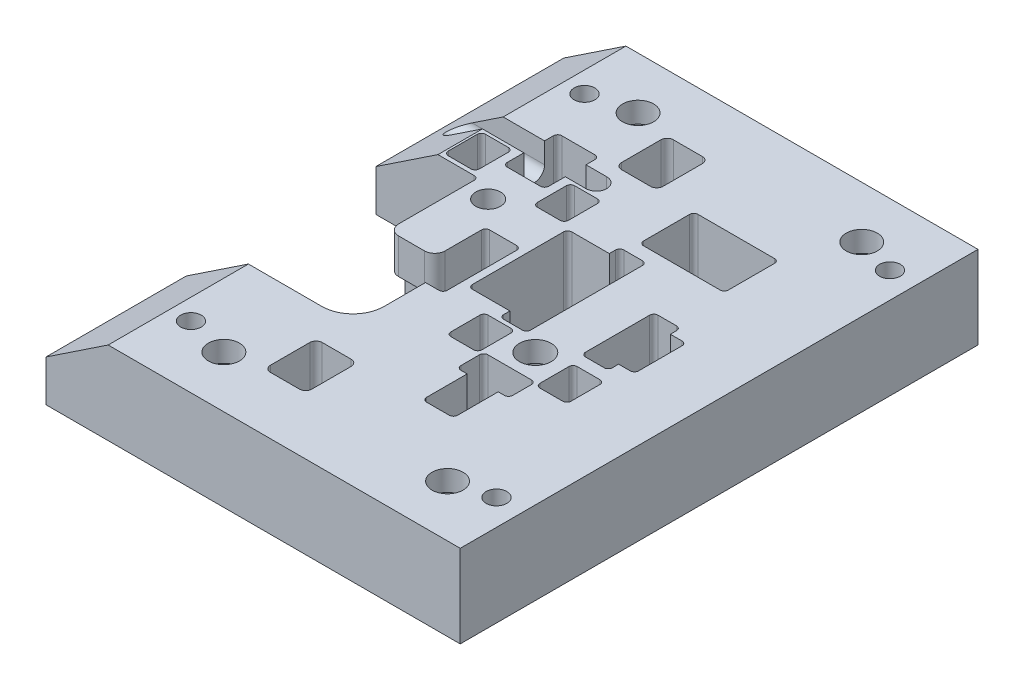
SolidWorks part; units mm, degrees
material "K110"
ref_plane "Front Plane" through (0, 0, 0) normal (0, 0, 1) x (1, 0, 0)
ref_plane "Top Plane" through (0, 0, 0) normal (0, 1, 0) x (1, 0, 0)
ref_plane "Right Plane" through (0, 0, 0) normal (1, 0, 0) x (0, 0, -1)
sketch "Sketch1" plane through (0, 0, 0) normal (0, 1, 0) x (1, 0, 0)
  line L1 (-100, -125) -> (100, -125)
  line L2 (-100, -125) -> (-100, 125)
  line L3 (-100, 125) -> (100, 125)
  line L4 (100, -125) -> (100, 125)
  line L5 (-100, -125) -> (100, 125) construction
  line L6 (-100, 125) -> (100, -125) construction
  point P0 (0, 0)
  dimension "D1" = 250
  dimension "D2" = 200
extrude "Boss-Extrude1" add sketch "Sketch1" along normal blind 40
sketch "Sketch2" plane through (0, 40, 0) normal (0, 1, 0) x (1, 0, 0)
  line L0 (17.25, 55.73) -> (55.25, 55.73) construction
  line L1 (15.75, 32.73) -> (15.75, -12.27) construction
  line L2 (58.25, 13.73) -> (58.25, -8.27) construction
  line L3 (30.25, -47.4) -> (42.25, -47.4) construction
  line L4 (17.25, 55.73) -> (55.25, 55.73)
  line L5 (15.75, 32.73) -> (15.75, -12.27)
  line L6 (58.25, 13.73) -> (58.25, -8.27)
  line L7 (30.25, -47.4) -> (42.25, -47.4)
sketch "Sketch3" plane through (0, 40, 0) normal (0, 1, 0) x (1, 0, 0)
  line L0 (30.25, -47.4) -> (42.25, -47.4) construction
  line L1 (28.75, -72.03) -> (43.75, -72.03)
  line L2 (28.75, -72.03) -> (28.75, -50.4)
  line L3 (23.75, -37.4) -> (48.75, -37.4)
  line L4 (43.75, -72.03) -> (43.75, -50.4)
  line L8 (36.25, -37.4) -> (36.25, -72.03) construction
  line L9 (36.25, 69.53) -> (36.25, -69.53) construction
  line L11 (43.75, -50.4) -> (48.75, -50.4)
  line L12 (48.75, -50.4) -> (48.75, -37.4)
  line L13 (28.75, -50.4) -> (23.75, -50.4)
  line L14 (23.75, -50.4) -> (23.75, -37.4)
  line L15 (66.38, -69.53) -> (-4.87, -69.53) construction
  dimension "D1" = 10
  dimension "D2" = 15
  dimension "D3" = 3
  dimension "D4" = 25
  dimension "D5" = 2.5
extrude "Cut-Extrude2" cut sketch "Sketch3" against normal up to next contours L3 L12 L11 L4 L1 L2 L13 L14
fillet "Fillet3" radius 2 6 edges at (43.75, 20, 72.03) (28.75, 20, 72.03) (48.75, 20, 50.4) (23.75, 20, 50.4) (48.75, 20, 37.4) (23.75, 20, 37.4)
sketch "Sketch4" plane through (0, 40, 0) normal (0, 1, 0) x (1, 0, 0)
  line L0 (48.25, -14.77) -> (61.25, -14.77)
  line L5 (61.25, -14.77) -> (61.25, -9.77)
  line L6 (64.38, 13.73) -> (58.25, 13.73) construction
  line L7 (66.38, 69.53) -> (66.38, -69.53) construction
  line L8 (66.38, 2.73) -> (51.7072, 2.73) construction
  line L9 (66.38, -6.27) -> (66.38, 11.73) construction
  line L10 (61.25, -9.77) -> (68.88, -9.77)
  line L11 (68.88, -9.77) -> (68.88, 15.23)
  line L13 (68.88, 15.23) -> (61.25, 15.23)
  line L14 (61.25, 15.23) -> (61.25, 20.23)
  line L15 (61.25, 20.23) -> (48.25, 20.23)
  line L16 (48.25, 20.23) -> (48.25, -14.77)
  line L17 (58.25, 13.73) -> (58.25, -8.27) construction
  dimension "D1" = 1.5
  dimension "D2" = 5
  dimension "D3" = 2.5
  dimension "D4" = 10
  dimension "D5" = 3
extrude "Cut-Extrude3" cut sketch "Sketch4" against normal up to next
fillet "Fillet4" radius 2 6 edges at (68.88, 20, 9.77) (68.88, 20, -15.23) (61.25, 20, -20.23) (48.25, 20, -20.23) (48.25, 20, 14.77) (61.25, 20, 14.77)
sketch "Sketch5" plane through (0, 40, 0) normal (0, 1, 0) x (1, 0, 0)
  line L0 (-7.37, -13.77) -> (12.75, -13.77)
  line L2 (12.75, -18.77) -> (25.75, -18.77)
  line L3 (25.75, -18.77) -> (25.75, 39.23)
  line L4 (25.75, 39.23) -> (12.75, 39.23)
  line L5 (12.75, 39.23) -> (12.75, 34.23)
  line L6 (12.75, 34.23) -> (-7.37, 34.23)
  line L7 (-7.37, 34.23) -> (-7.37, -13.77)
  line L8 (15.75, 32.73) -> (15.75, -12.27) construction
  line L9 (-4.87, 69.53) -> (-4.87, -69.53) construction
  line L10 (-4.87, 10.23) -> (25.75, 10.23) construction
  line L11 (-4.87, 26.73) -> (-4.87, -6.27) construction
  line L12 (12.75, -18.77) -> (12.75, -13.77)
  line L13 (1.13, -12.27) -> (15.75, -12.27) construction
  line L17 (-18, -8.27) -> (-18, 13.73) construction
  line L18 (-18, 2.73) -> (-15, 2.73) construction
  dimension "D1" = 3
  dimension "D2" = 10
  dimension "D3" = 2.5
  dimension "D4" = 1.5
  dimension "D5" = 5
extrude "Cut-Extrude4" cut sketch "Sketch5" against normal up to next
fillet "Fillet5" radius 2 6 edges at (25.75, 20, -39.23) (12.75, 20, 18.77) (25.75, 20, 18.77) (-7.37, 20, 13.77) (12.75, 20, -39.23) (-7.37, 20, -34.23)
sketch "Sketch6" plane through (0, 40, 0) normal (0, 1, 0) x (1, 0, 0)
  line L0 (15.75, 72.03) -> (15.75, 45.73)
  line L3 (15.75, 45.73) -> (56.75, 45.73)
  line L6 (56.75, 45.73) -> (56.75, 72.03)
  line L7 (56.75, 72.03) -> (15.75, 72.03)
  line L8 (36.25, 69.53) -> (36.25, 45.73) construction
  line L9 (36.25, 69.53) -> (36.25, -69.53) construction
  line L10 (66.38, 69.53) -> (-4.87, 69.53) construction
  line L12 (17.25, 55.73) -> (55.25, 55.73) construction
  dimension "D1" = 2.5
  dimension "D2" = 41
  dimension "D5" = 10
extrude "Cut-Extrude5" cut sketch "Sketch6" against normal up to next
fillet "Fillet6" radius 2 4 edges at (15.75, 20, -72.03) (56.75, 20, -72.03) (15.75, 20, -45.73) (56.75, 20, -45.73)
sketch "Sketch7" plane through (0, 40, 0) normal (0, 1, 0) x (1, 0, 0)
  line L0 (57.75, -29.77) -> (57.75, -32.27) construction
  line L3 (60.25, -29.77) -> (55.25, -29.77) construction
  line L4 (60.25, -27.27) -> (60.25, -32.27) construction
  line L5 (55.25, -11.27) -> (55.25, -38.4) construction
  line L7 (63.25, -20.77) -> (52.25, -20.77)
  line L8 (65.25, -22.77) -> (65.25, -36.77)
  line L9 (63.25, -38.77) -> (52.25, -38.77)
  line L10 (50.25, -22.77) -> (50.25, -36.77)
  arc A2 (52.25, -38.77) -> (50.25, -36.77) centre (52.25, -36.77) cw
  arc A3 (65.25, -36.77) -> (63.25, -38.77) centre (63.25, -36.77) cw
  arc A4 (63.25, -20.77) -> (65.25, -22.77) centre (63.25, -22.77) cw
  arc A5 (52.25, -20.77) -> (50.25, -22.77) centre (52.25, -22.77) ccw
  point P14 (50.25, -38.77)
  point P17 (65.25, -38.77)
  point P20 (65.25, -20.77)
  dimension "D4" = 2
  dimension "D1" = 2.5
  dimension "D2" = 18
  dimension "D3" = 15
  dimension "D5" = 9
extrude "Cut-Extrude6" cut sketch "Sketch7" against normal up to next
sketch "Sketch8" plane through (0, 40, 0) normal (0, 1, 0) x (1, 0, 0)
  line L0 (12.25, -29.77) -> (17.25, -29.77) construction
  line L3 (12.25, -32.27) -> (12.25, -27.27) construction
  line L4 (63.25, -20.77) -> (52.25, -20.77) construction
  line L7 (17.25, -38.4) -> (17.25, -13.77) construction
  line L8 (14.75, -29.77) -> (14.75, -32.27) construction
  line L9 (52.25, -38.77) -> (63.25, -38.77) construction
  line L10 (9.25, -20.77) -> (20.25, -20.77)
  line L11 (7.25, -22.77) -> (7.25, -36.77)
  line L12 (9.25, -38.77) -> (20.25, -38.77)
  line L13 (22.25, -22.77) -> (22.25, -36.77)
  arc A2 (7.25, -36.77) -> (9.25, -38.77) centre (9.25, -36.77) ccw
  arc A3 (20.25, -38.77) -> (22.25, -36.77) centre (20.25, -36.77) ccw
  arc A4 (20.25, -20.77) -> (22.25, -22.77) centre (20.25, -22.77) cw
  arc A5 (9.25, -20.77) -> (7.25, -22.77) centre (9.25, -22.77) ccw
  dimension "D1" = 2.5
  dimension "D2" = 2
extrude "Cut-Extrude7" cut sketch "Sketch8" against normal up to next
sketch "Sketch21" plane through (0, 40, 0) normal (0, 1, 0) x (1, 0, 0)
  line L0 (-21, 55.73) -> (-21, 16.73) construction
  line L3 (-24, 54.23) -> (-13, 54.23)
  line L4 (-26, 52.23) -> (-26, 38.23)
  line L5 (-24, 36.23) -> (-13, 36.23)
  line L6 (-11, 52.23) -> (-11, 38.23)
  line L7 (-21, 55.73) -> (-59, 55.73) construction
  line L9 (-16, 45.23) -> (-21, 45.23) construction
  line L10 (-18.5, 45.23) -> (-18.5, 54.23) construction
  line L11 (-40, 55.73) -> (-40, 36.23) construction
  line L12 (-16, 42.73) -> (-16, 47.73) construction
  line L16 (-69, 52.23) -> (-69, 38.23)
  line L17 (-56, 36.23) -> (-67, 36.23)
  line L18 (-54, 52.23) -> (-54, 38.23)
  line L19 (-56, 54.23) -> (-67, 54.23)
  arc A2 (-26, 38.23) -> (-24, 36.23) centre (-24, 38.23) ccw
  arc A3 (-13, 36.23) -> (-11, 38.23) centre (-13, 38.23) ccw
  arc A4 (-13, 54.23) -> (-11, 52.23) centre (-13, 52.23) cw
  arc A5 (-24, 54.23) -> (-26, 52.23) centre (-24, 52.23) ccw
  arc A6 (-56, 54.23) -> (-54, 52.23) centre (-56, 52.23) cw
  arc A7 (-67, 54.23) -> (-69, 52.23) centre (-67, 52.23) ccw
  arc A8 (-67, 36.23) -> (-69, 38.23) centre (-67, 38.23) cw
  arc A9 (-54, 38.23) -> (-56, 36.23) centre (-56, 38.23) cw
  dimension "D4" = 15
  dimension "D2" = 2
  dimension "D1" = 2.5
  dimension "D3" = 18
extrude "Cut-Extrude12" cut sketch "Sketch21" against normal up to next
sketch "Sketch22" plane through (0, 40, 0) normal (0, 1, 0) x (1, 0, 0)
  line L0 (-100, 125) -> (-100, -125) construction
  line L1 (-100, 55.73) -> (-15, 55.73)
  line L2 (-100, 55.73) -> (-100, 65.726)
  line L3 (-100, 65.726) -> (-15, 65.726)
  line L4 (-15, 55.73) -> (-15, 65.726)
  line L5 (-21, 55.73) -> (-59, 55.73) construction
  line L6 (-59, 63.776) -> (-21, 63.776) construction
  line L7 (-21, 55.73) -> (-21, 61.5256) construction
  line L8 (-15, 60.728) -> (-100, 60.728) construction
  dimension "D1" = 1.95
  dimension "D2" = 6
ref_plane "Plane1" through (0, 0, -60.728) normal (0, 0, -1) x (-1, 0, 0)
sketch "Sketch24" plane through (0, 0, -60.728) normal (0, 0, -1) x (-1, 0, 0)
  line L0 (15, 40) -> (15, 35)
  line L1 (15, 40) -> (100, 40) construction
  line L2 (25, 25) -> (100, 25)
  line L3 (100, 40) -> (100, 0) construction
  line L4 (15, 40) -> (100, 40)
  line L5 (100, 40) -> (100, 25)
  arc A0 (15, 35) -> (25, 25) centre (25, 35) ccw
  dimension "D2" = 10
  dimension "D1" = 15
extrude "Cut-Extrude15" cut sketch "Sketch24" against normal mid plane 10
fillet "Fillet9" 2 edges at (-62.5, 25, -55.728) (-62.5, 25, -65.728) type full round first side face at (-50.5858, 32.5858, -55.728) second side face at (-50.5858, 32.5858, -65.728) middle face at (-62.5, 25, -60.728)
sketch "Sketch23" plane through (0, 40, 0) normal (0, 1, 0) x (1, 0, 0)
  line L0 (-40, 55.73) -> (-40, 45.73) construction
  line L1 (-48, 72.03) -> (-32, 72.03)
  line L2 (-50, 70.03) -> (-50, 47.73)
  line L3 (-48, 45.73) -> (-32, 45.73)
  line L4 (-30, 70.03) -> (-30, 47.73)
  line L5 (-21, 55.73) -> (-59, 55.73) construction
  line L6 (17.75, 45.73) -> (54.75, 45.73) construction
  line L7 (54.75, 72.03) -> (17.75, 72.03) construction
  arc A0 (-50, 47.73) -> (-48, 45.73) centre (-48, 47.73) ccw
  arc A1 (-48, 72.03) -> (-50, 70.03) centre (-48, 70.03) ccw
  arc A2 (-32, 72.03) -> (-30, 70.03) centre (-32, 70.03) cw
  arc A3 (-32, 45.73) -> (-30, 47.73) centre (-32, 47.73) ccw
  point P14 (-50, 45.73)
  point P21 (-30, 45.73)
  dimension "D2" = 2
  dimension "D1" = 20
extrude "Cut-Extrude14" cut sketch "Sketch23" against normal up to next
sketch "Sketch26" plane through (0, 40, 0) normal (0, 1, 0) x (1, 0, 0)
  line L0 (-100, 55.728) -> (-100, -125) construction
  line L1 (-100, 34.23) -> (-50.5, 34.23)
  line L2 (-100, 34.23) -> (-100, -57.27)
  line L3 (-100, -57.27) -> (-19.5, -57.27)
  line L4 (-19.5, -22.27) -> (-19.5, -57.27)
  line L5 (-60.5, 32.73) -> (-66.5, 32.73) construction
  line L6 (-50.5, 34.23) -> (-50.5, -9.27)
  line L7 (-50.5, -9.27) -> (-28, -9.27)
  line L8 (-59, -19.27) -> (-21, -19.27) construction
  line L9 (-21, -11.27) -> (-21, -19.27) construction
  line L10 (-28, -9.27) -> (-28, 15.23)
  line L11 (-60.5, -12.27) -> (-60.5, 32.73) construction
  line L12 (-19.5, -22.27) -> (-11, -22.27)
  line L13 (-11, -22.27) -> (-11, 15.23)
  line L14 (-28, 15.23) -> (-11, 15.23)
  line L15 (-18, -8.27) -> (-18, 13.73) construction
  line L16 (-12, 13.73) -> (-18, 13.73) construction
  dimension "D1" = 1.5
  dimension "D2" = 10
  dimension "D3" = 1.5
  dimension "D4" = 35
  dimension "D5" = 10
  dimension "D6" = 1.5
  dimension "D7" = 3
  dimension "D8" = 10
  dimension "D9" = 7
extrude "Cut-Extrude16" cut sketch "Sketch26" against normal up to next contours L1 L6 L7 L10 L14 L13 L12 L4 L3 L2
fillet "Fillet10" radius 2 4 edges at (-11, 20, 22.27) (-50.5, 20, -34.23) (-11, 20, -15.23) (-28, 20, -15.23)
sketch "Sketch27" plane through (-50.5, 0, 0) normal (-1, 0, 0) x (0, 0, 1)
  line L0 (-32.23, 0) -> (9.27, 0) construction
  line L1 (1.27, 0) -> (9.27, 0)
  line L2 (1.27, 0) -> (1.27, 23)
  line L3 (1.27, 23) -> (9.27, 23)
  line L4 (9.27, 0) -> (9.27, 23)
  line L5 (9.27, 23) -> (9.27, 0) construction
  dimension "D1" = 23
  dimension "D2" = 8
extrude "Cut-Extrude17" cut sketch "Sketch27" against normal blind 18.5 contours L4 L3 L2 L1
fillet "Fillet11" radius 3 3 edges at (-32, 23, 5.27) (-41.25, 23, 1.27) (-32, 11.5, 1.27)
fillet "Fillet12" radius 15 1 edges at (-19.5, 20, 57.27)
fillet "Fillet13" radius 5 2 edges at (-50.5, 31.5, 9.27) (-28, 20, 9.27)
chamfer "Chamfer1" distance 20 distance2 30 2 edges at (-100, 40, -44.979) (-100, 40, 91.135) first distance on face at (-100, 26.875, -70.1715) first distance on face at (-100, 20, 91.135)
sketch "Sketch28" plane through (0, 40, 0) normal (0, 1, 0) x (1, 0, 0)
  line L0 (-14.87, 84.765) -> (-9.87, 84.765) construction
  line L1 (-19.37, 97.265) -> (-5.37, 97.265)
  line L2 (-22.37, 94.265) -> (-22.37, 75.265)
  line L3 (-19.37, 72.265) -> (-5.37, 72.265)
  line L4 (-2.37, 94.265) -> (-2.37, 75.265)
  line L5 (-14.87, 95) -> (-14.87, 74.53) construction
  line L6 (-9.87, 50.73) -> (-9.87, 95) construction
  line L7 (-12.37, 84.765) -> (-12.37, 92.265) construction
  line L8 (-12.37, 92.265) -> (-12.37, 77.265) construction
  line L9 (-9.64, 92.265) -> (-9.64, 77.265) construction
  line L10 (-15.1, 92.265) -> (-15.1, 77.265) construction
  arc A0 (-9.64, 92.265) -> (-15.1, 92.265) centre (-12.37, 92.265) ccw construction
  arc A1 (-15.1, 77.265) -> (-9.64, 77.265) centre (-12.37, 77.265) ccw construction
  arc A2 (-22.37, 75.265) -> (-19.37, 72.265) centre (-19.37, 75.265) ccw
  arc A3 (-5.37, 72.265) -> (-2.37, 75.265) centre (-5.37, 75.265) ccw
  arc A4 (-5.37, 97.265) -> (-2.37, 94.265) centre (-5.37, 94.265) cw
  arc A5 (-19.37, 97.265) -> (-22.37, 94.265) centre (-19.37, 94.265) ccw
  point P12 (-12.37, 84.765)
  point P26 (-2.37, 72.265)
  point P29 (-2.37, 97.265)
  point P32 (-22.37, 97.265)
  dimension "D4" = 2.73
  dimension "D5" = 3
  dimension "D1" = 25
  dimension "D2" = 20
  dimension "D3" = 15
extrude "Cut-Extrude18" cut sketch "Sketch28" against normal up to next
mirror "Mirror1" about plane through (0, 0, 0) normal (0, 0, 1) of "Cut-Extrude18"
sketch "Sketch30" plane through (0, 40, 0) normal (0, 1, 0) x (1, 0, 0)
  line L1 (25.75, -37.4) -> (46.75, -37.4) construction
  line L2 (-22, 0) -> (22, 0) construction
  circle A0 centre (36.25, -25) radius 7.6846
  point P5 (36.25, -37.4)
  dimension "D1" = 25
extrude "Cut-Extrude19" cut sketch "Sketch30" against normal up to next
sketch "Sketch31" plane through (0, 0, 0) normal (0, -1, 0) x (1, 0, 0)
  circle A0 centre (36.25, 25) radius 10
  dimension "D1" = 20
extrude "Cut-Extrude20" cut sketch "Sketch31" against normal blind 30
sketch "Sketch33" plane through (0, 40, 0) normal (0, 1, 0) x (1, 0, 0)
  line L0 (-39.25, -9.27) -> (-39.25, 45.73) construction
  line L1 (-45.5, -9.27) -> (-33, -9.27) construction
  line L2 (-48, 45.73) -> (-32, 45.73) construction
  line L3 (-26, 15.23) -> (-13, 15.23) construction
  circle A0 centre (-39.25, 27.73) radius 6
  dimension "D1" = 12
  dimension "D2" = 12.5
extrude "Cut-Extrude21" cut sketch "Sketch33" against normal up to next contours A0
sketch "Sketch34" plane through (0, 0, 0) normal (0, -1, 0) x (1, 0, 0)
  circle A0 centre (-39.25, -27.73) radius 9
  dimension "D1" = 18
extrude "Cut-Extrude22" cut sketch "Sketch34" against normal blind 31
hole_wizard "M10 Tapped Hole1" positions "Sketch37" profile "Sketch36" tap size "M10" standard "ISO"
sketch "Sketch37" plane through (0, 0, 0) normal (0, -1, 0) x (-1, 0, 0)
  line L0 (-100, 125) -> (100, 125) construction
  line L1 (-100, -125) -> (-100, 125) construction
  line L2 (100, 125) -> (100, 34.23) construction
  line L3 (100, -125) -> (-100, -125) construction
  point P0 (-87.5, 112.5)
  point P2 (60, 112.5)
  point P4 (60, -112.5)
  point P6 (-87.5, -112.5)
  point P15 (-94.777, 110.6257)
  point P16 (0, 0)
  point P21 (0, 0)
  point P22 (0, 0)
  point P25 (0, 0)
  point P26 (0, 0)
  dimension "D1" = 12.5
  dimension "D2" = 12.5
  dimension "D3" = 40
  dimension "D4" = 12.5
sketch "Sketch36" plane through (87.5, 0, -112.5) normal (1, 0, 0) x (0, 0, -1)
  line L0 (0, 0) -> (0, 30.0537)
  line L1 (0, 30.0537) -> (4.25, 27.5)
  line L2 (4.25, 27.5) -> (4.25, 0.775)
  line L3 (4.25, 0.775) -> (5.025, 0)
  line L5 (5.025, 0) -> (0, 0)
  line L6 (-4.25, 0.775) -> (-5.025, 0) construction
  line L10 (0, 30.0537) -> (-4.25, 27.5) construction
  line L11 (0, -6.35) -> (0, 107.95) construction
  dimension "Tap Drill Dia." = 8.5
  dimension "Tap Drill Depth" = 27.5
  dimension "Near C'Sink Dia." = 10.05
  dimension "Near C'Sink Angle" = 90
  dimension "Drill Angle" = 118
cosmetic thread "Hole Thread1" parameters "D1"=20, "D2"=10
cosmetic thread "Hole Thread2" parameters "D1"=20, "D2"=10
cosmetic thread "Hole Thread3" parameters "D1"=20, "D2"=10
cosmetic thread "Hole Thread4" parameters "D1"=20, "D2"=10
hole_wizard "Ø10.0mm Dowel Hole1" positions "Sketch40" profile "Sketch39" hole size "Ø10.0" standard "ISO" end condition through all
sketch "Sketch40" plane through (0, 0, 0) normal (0, -1, 0) x (-1, 0, 0)
  line L0 (-100, -125) -> (-100, 125) construction
  line L1 (100, 125) -> (100, 34.23) construction
  circle A0 centre (-87.5, 112.5) radius 4.25 construction
  circle A1 centre (-87.5, -112.5) radius 4.25 construction
  point P0 (-87.5, 95)
  point P2 (60, 95)
  point P4 (60, -95)
  point P6 (-87.5, -95)
  point P17 (0, 0)
  point P18 (0, 0)
  point P19 (0, 0)
  point P20 (0, 0)
  dimension "D4" = 17.5
  dimension "D1" = 17.5
  dimension "D2" = 12.5
  dimension "D3" = 40
sketch "Sketch39" plane through (87.5, 0, -95) normal (1, 0, 0) x (0, 0, -1)
  line L0 (0, 0) -> (0, 40)
  line L1 (0, 40) -> (5, 40)
  line L2 (5, 40) -> (5, 0)
  line L5 (5, 0) -> (0, 0)
  line L11 (0, -6.35) -> (0, 107.95) construction
  dimension "Thru Hole Dia." = 10
  dimension "Thru Hole Depth" = 40
sketch "Sketch41" plane through (0, 40, 0) normal (0, 1, 0) x (1, 0, 0)
  line L0 (-9.87, -95) -> (452.63, -95) construction
  line L1 (71.38, -71.53) -> (66.38, -71.53) construction
  line L2 (68.88, -71.53) -> (68.88, -100) construction
  line L3 (-22, 0) -> (22, 0) construction
  circle A0 centre (68.88, -100) radius 7.5
  circle A1 centre (-39.12, -100) radius 7.5
  circle A2 centre (68.88, 100) radius 7.5
  circle A3 centre (-39.12, 100) radius 7.5
  point P11 (0, 0)
  dimension "D2" = 15
  dimension "D1" = 5
  dimension "D3" = 108
extrude "Cut-Extrude23" cut sketch "Sketch41" against normal up to next
sketch "Sketch42" plane through (0, 0, 0) normal (0, -1, 0) x (1, 0, 0)
  circle A0 centre (68.88, 100) radius 9
  circle A1 centre (-39.12, 100) radius 9
  circle A2 centre (68.88, -100) radius 9
  circle A3 centre (-39.12, -100) radius 9
  dimension "D1" = 18
extrude "Cut-Extrude24" cut sketch "Sketch42" against normal blind 30
